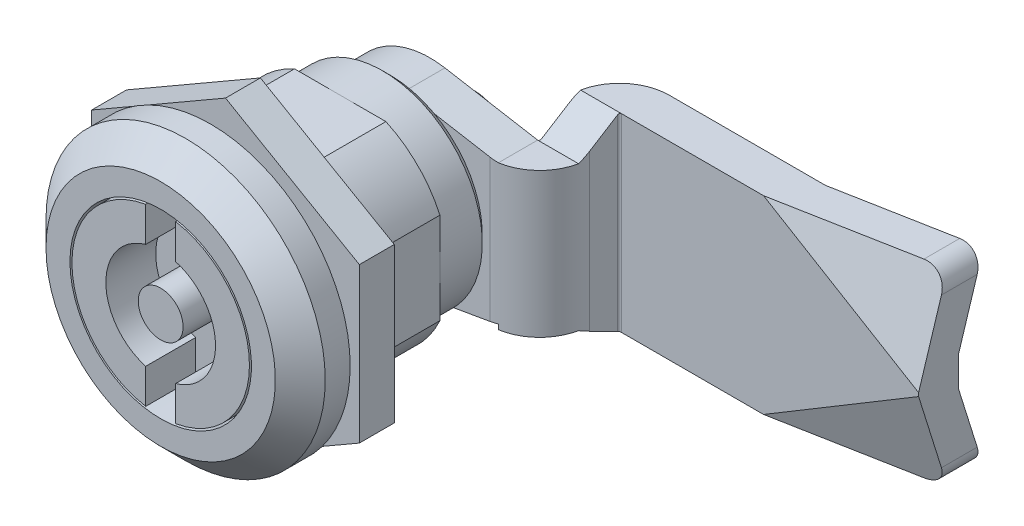
SolidWorks part; units mm, degrees
material "Alloy Steel"
ref_plane "Front Plane" through (0, 0, 0) normal (0, 0, 1) x (1, 0, 0)
ref_plane "Top Plane" through (0, 0, 0) normal (0, 1, 0) x (1, 0, 0)
ref_plane "Right Plane" through (0, 0, 0) normal (1, 0, 0) x (0, 0, -1)
sketch "Sketch1" plane through (0, 0, 0) normal (0, 0, 1) x (1, 0, 0)
  circle A0 centre (0, 0) radius 14
  dimension "D1" = 28
extrude "Extrude1" add sketch "Sketch1" against normal blind 5
sketch "Sketch2" plane through (0, 0, -5) normal (0, 0, -1) x (-1, 0, 0)
  line L0 (0, 0) -> (0, 14) construction
  line L1 (0, 0) -> (14, 0) construction
  line L2 (4.5826, -10) -> (-4.5826, -10)
  line L3 (10, -4.5826) -> (10, 4.5826)
  line L4 (4.5826, 10) -> (-4.5826, 10)
  line L5 (-10, -4.5826) -> (-10, 4.5826)
  arc A0 (-10, -4.5826) -> (-4.5826, -10) centre (0, 0) ccw
  arc A1 (-4.5826, 10) -> (-10, 4.5826) centre (0, 0) ccw
  arc A2 (10, 4.5826) -> (4.5826, 10) centre (0, 0) ccw
  arc A3 (4.5826, -10) -> (10, -4.5826) centre (0, 0) ccw
  circle A4 centre (0, 0) radius 14 construction
  dimension "D1" = 22
  dimension "D3" = 20
  dimension "D2" = 20
extrude "Extrude2" add sketch "Sketch2" along normal blind 18
ref_plane "Plane1" through (0, 0, -25) normal (0, 0, 1) x (1, 0, 0)
ref_plane "Plane2" through (0, 0, -6.5) normal (0, 0, -1) x (-1, 0, 0)
sketch "Sketch7" plane through (0, 0, -6.5) normal (0, 0, -1) x (-1, 0, 0)
  line L1 (0, 15.5) -> (-13.4234, 7.75)
  line L2 (-13.4234, 7.75) -> (-13.4234, -7.75)
  line L3 (-13.4234, -7.75) -> (0, -15.5)
  line L4 (0, -15.5) -> (13.4234, -7.75)
  line L5 (13.4234, -7.75) -> (13.4234, 7.75)
  line L6 (13.4234, 7.75) -> (0, 15.5)
  circle A0 centre (0, 0) radius 13.4234 construction
  circle A1 centre (0, 0) radius 11.1
  dimension "D2" = 22.2
  dimension "D1" = 31
extrude "Extrude6" add sketch "Sketch7" along normal blind 3.5 separate body
sketch "Sketch10" plane through (0, 0, 0) normal (1, 0, 0) x (0, 0, -1)
  line L0 (0, 11.5) -> (0, 14)
  line L1 (0, 14) -> (0, -14) construction
  line L2 (0, 14) -> (2.5, 14)
  line L3 (2.5, 14) -> (0, 11.5)
  line L4 (5, 14) -> (0, 14) construction
  dimension "D1" = 2.5
  dimension "D2" = 2.5
revolve "Cut-Revolve1" cut sketch "Sketch10" angle 360 about axis through (0, 0, -5) along (0, 0, 1)
sketch "Sketch6" plane through (0, 0, 0) normal (0, 0, 1) x (1, 0, 0)
  line L0 (-1.5, 8.8741) -> (-1.5, -8.8741)
  line L1 (1.5, 8.8741) -> (1.5, -8.8741)
  line L2 (0, 0) -> (0, 5.8757) construction
  circle A0 centre (0, 0) radius 2.25
  circle A1 centre (0, 0) radius 5.5
  arc A3 (1.5, 8.8741) -> (-1.5, 8.8741) centre (0, 0) ccw
  arc A4 (-1.5, -8.8741) -> (1.5, -8.8741) centre (0, 0) ccw
  circle A5 centre (0, 0) radius 9 construction
  circle A6 centre (0, 0) radius 11.5 construction
  dimension "D1" = 3
  dimension "D2" = 11
  dimension "D3" = 2.5
  dimension "D4" = 4.5
extrude "Extrude5" cut sketch "Sketch6" against normal blind 5
sketch "Sketch11" plane through (0, 0, 0) normal (0, 1, 0) x (1, 0, 0)
  line L0 (-4.5826, 23) -> (-10, 23) construction
  line L1 (-10, 23) -> (10, 23)
  line L2 (-10, 23) -> (-10, 27)
  line L3 (16, 35) -> (45, 35)
  line L4 (45, 31) -> (45, 35)
  line L5 (0, 0) -> (0, 40.2207) construction
  line L6 (-10, 23) -> (-10, 5) construction
  line L8 (-10, 27) -> (10.8, 27)
  line L9 (11, 30) -> (11, 27.2)
  line L12 (45, 31) -> (15.2, 31)
  line L13 (15, 28) -> (15, 30.8)
  arc A0 (11, 27.2) -> (10.8, 27) centre (10.8, 27.2) cw
  arc A1 (15, 30.8) -> (15.2, 31) centre (15.2, 30.8) cw
  arc A2 (10, 23) -> (15, 28) centre (10, 28) ccw
  arc A3 (16, 35) -> (11, 30) centre (16, 30) ccw
  point P21 (15, 23)
  dimension "D7" = 0.2
  dimension "D8" = 5
  dimension "D1" = 4
  dimension "D2" = 8
  dimension "D3" = 4
  dimension "D4" = 4
  dimension "D5" = 25
  dimension "D6" = 45
extrude "Extrude9" add sketch "Sketch11" along normal mid plane 19 separate body
fillet "Fillet1" radius 8 2 edges at (-10, -9.5, -25) (-10, 9.5, -25)
fillet "Fillet2" radius 3 2 edges at (45, -9.5, -33) (45, 9.5, -33)
sketch "Sketch12" plane through (0, 0, -27) normal (0, 0, -1) x (-1, 0, 0)
  line L5 (-10.8, 9.5) -> (-10.8, -9.5) construction
  line L7 (-10.8, 7) -> (-1.502, 8.6201)
  line L8 (-10.8, -7) -> (-1.502, -8.6201)
  line L9 (-10.8, 7) -> (-10.8, 10.5)
  line L10 (-10.8, 10.5) -> (10.2, 10.5)
  line L11 (10.2, 10.5) -> (10.2, -10.5)
  line L12 (10.2, -10.5) -> (-10.8, -10.5)
  line L13 (-10.8, -10.5) -> (-10.8, -7)
  line L14 (-10.8, 7) -> (-10.8, -7) construction
  arc A0 (-1.502, -8.6201) -> (-1.502, 8.6201) centre (0, 0) ccw
  point P6 (10.2, 0)
  point P14 (-10.8, 0)
  dimension "D1" = 17.5
  dimension "D4" = 21
  dimension "D2" = 14
  dimension "D3" = 21
extrude "Cut-Extrude1" cut sketch "Sketch12" against normal blind 4
sketch "Sketch14" plane through (10.8, 0, 0) normal (-1, 0, 0) x (0, 0, 1)
  line L0 (-31, 9.5) -> (-23, 9.5)
  line L1 (-23, 10) -> (-23, 4.5826) construction
  line L2 (-23, -8.75) -> (-23, 8.75) construction
  line L3 (-23, 9.5) -> (-23, 7)
  line L5 (-31, -9.5) -> (-23, -9.5)
  line L6 (-23, -4.5826) -> (-23, -10) construction
  line L7 (-23, -9.5) -> (-23, -7.5)
  line L9 (-23, 7) -> (-27, 7)
  line L10 (-27, 7) -> (-31, 9.5)
  line L11 (-23, -7.5) -> (-27, -7.5)
  line L12 (-27, 8.75) -> (-27, -8.75) construction
  line L13 (-27, 7) -> (-27, -7) construction
  line L14 (-27, -7.5) -> (-31, -9.5)
  line L15 (-27, -9.5) -> (-23.0644, -9.5) construction
  line L16 (-30, 9.5) -> (-35, 9.5) construction
  point P14 (-25, -7.5)
  dimension "D1" = 2
  dimension "D2" = 8
extrude "Cut-Extrude2" cut sketch "Sketch14" against normal blind 5
sketch "Sketch17" plane through (45, 0, 0) normal (1, 0, 0) x (0, 0, -1)
  line L0 (27, 7) -> (27, 8.6201) construction
  line L1 (31, 9.5) -> (37.5, 9.5)
  line L2 (31, 9.5) -> (31, -9.5)
  line L3 (31, -9.5) -> (37.5, -9.5)
  line L4 (37.5, 9.5) -> (37.5, -9.5)
  dimension "D1" = 19
  dimension "D2" = 10.5
extrude "Boss-Extrude1" add sketch "Sketch17" against normal blind 15
sketch "Sketch18" plane through (0, 0, -37.5) normal (0, 0, -1) x (-1, 0, 0)
  line L0 (-30, 9.5) -> (-30, -9.5)
  line L1 (-30, -9.5) -> (-45, -9.5) construction
  line L2 (-30, -9.5) -> (-30, 9.5) construction
  line L3 (-30, -9.5) -> (-45, -1.5)
  line L4 (-45, -9.5) -> (-45, 9.5) construction
  line L5 (-45, -1.5) -> (-45, 1.5)
  line L6 (-45, 1.5) -> (-30, 9.5)
  point P7 (-45, 0)
  dimension "D1" = 3
extrude "Cut-Extrude4" cut sketch "Sketch18" against normal blind 2.5
ref_plane "Plane4" through (33.75, -20.25, 0) normal (0.8575, -0.5145, 0) x (0, 0, -1)
ref_plane "Plane3" through (33.75, 20.25, 0) normal (0.8575, 0.5145, 0) x (0, 0, -1)
sketch "Sketch20" plane through (33.75, 20.25, 0) normal (0.8575, 0.5145, 0) x (0, 0, -1)
  line L8 (35, -23.5811) -> (37.5, -23.5811)
  line L9 (37.5, -23.5811) -> (37.5, -24.4385)
  line L11 (31, -31.2985) -> (33.9155, -31.2985)
  line L12 (31, -31.2985) -> (37.5, -31.2985) construction
  line L14 (31, -15.0061) -> (31, -31.2985) construction
  line L15 (31, -23.2985) -> (31, -31.2985)
  line L20 (37.5, -31.2985) -> (37.5, -24.4385)
  line L23 (31, -23.2985) -> (33.9155, -31.2985)
  line L24 (35, -23.5811) -> (35, -24.4385)
  line L25 (35, -24.4385) -> (37.5, -31.2985)
  line L26 (35, -21.8661) -> (35, -24.4385) construction
  point P17 (35, -24.0098)
  dimension "D1" = 8
  dimension "D2" = 4
extrude "Cut-Extrude8" cut sketch "Sketch20" against normal through all
sketch "Sketch21" plane through (33.75, -20.25, 0) normal (0.8575, -0.5145, 0) x (0, 0, -1)
  line L0 (31, 31.2985) -> (31, 23.2985)
  line L1 (31, 23.2985) -> (33.9155, 31.2985)
  line L2 (37.5, 31.2985) -> (31, 31.2985) construction
  line L3 (33.9155, 31.2985) -> (31, 31.2985)
  line L4 (37.5, 23.5811) -> (35, 23.5811)
  line L9 (37.5, 31.2985) -> (37.5, 23.5811)
  line L10 (35, 23.5811) -> (35, 24.4385)
  line L11 (35, 24.4385) -> (37.5, 31.2985)
  line L13 (35, 24.4385) -> (35, 21.8661) construction
  dimension "D1" = 8
  dimension "D2" = 4
extrude "Cut-Extrude9" cut sketch "Sketch21" against normal through all
fillet "Fillet3" radius 2 2 edges at (45, -9.5, -35.7077) (45, 9.5, -35.7077)
sketch "Sketch23" plane through (0, 0, 0) normal (0, 1, 0) x (1, 0, 0)
  line L0 (0, 27) -> (0, 30)
  line L1 (1.502, 27) -> (-8.75, 27) construction
  line L2 (0, 30) -> (-3, 30)
  line L3 (0, 27) -> (-5.5, 27)
  line L4 (-5.5, 27) -> (-5.5, 27.5)
  line L5 (-3, 30) -> (-5.5, 27.5)
  dimension "D1" = 5.5
  dimension "D2" = 3
  dimension "D3" = 0.5
  dimension "D4" = 3
revolve "Revolve1" add sketch "Sketch23" angle 360 about L0
sketch "Sketch24" plane through (0, 0, -27) normal (0, 0, -1) x (-1, 0, 0)
  line L0 (10, -4.5826) -> (10, 4.5826) construction
  line L1 (4, 2.3094) -> (0, 4.6188)
  line L2 (0, 4.6188) -> (-4, 2.3094)
  line L3 (-4, 2.3094) -> (-4, -2.3094)
  line L4 (-4, -2.3094) -> (0, -4.6188)
  line L5 (0, -4.6188) -> (4, -2.3094)
  line L6 (4, -2.3094) -> (4, 2.3094)
  circle A0 centre (0, 0) radius 4 construction
  dimension "D1" = 8
extrude "Boss-Extrude3" add sketch "Sketch24" along normal blind 4.5
ref_axis "Axis1" through (0, 0, -5) along (0, 0, 1)
ref_plane "Plane5" through (0, 0, 0) normal (-0.5, 0.866, 0) x (-0.866, -0.5, 0)
sketch "Sketch26" plane through (0, 0, 0) normal (-0.5, 0.866, 0) x (-0.866, -0.5, 0)
  line L0 (4.6188, -31.5) -> (3.6188, -31.5)
  line L1 (4.6188, -31.5) -> (2.3094, -31.5) construction
  line L2 (3.6188, -31.5) -> (4.6188, -30.5)
  line L3 (4.6188, -31.5) -> (4.6188, -28.3812) construction
  line L4 (4.6188, -30.5) -> (4.6188, -31.5)
  dimension "D1" = 1
  dimension "D2" = 1
revolve "Cut-Revolve4" cut sketch "Sketch26" angle 360 about axis through (0, 0, -5) along (0, 0, 1)
sketch "Sketch28" plane through (0, 0, -31.5) normal (0, 0, -1) x (-1, 0, 0)
  circle A0 centre (0, 0) radius 3.4
  dimension "D1" = 6.8
extrude "Cut-Extrude11" cut sketch "Sketch28" against normal blind 0.1
sketch "Sketch29" plane through (0, 0, -31.5) normal (0, 0, -1) x (-1, 0, 0)
  line L1 (-5, -0.4) -> (5, -0.4)
  line L2 (-5, -0.4) -> (-5, 0.4)
  line L3 (-5, 0.4) -> (5, 0.4)
  line L4 (5, -0.4) -> (5, 0.4)
  line L5 (-5, -0.4) -> (5, 0.4) construction
  line L6 (-5, 0.4) -> (5, -0.4) construction
  point P0 (0, 0)
  dimension "D1" = 0.8
  dimension "D2" = 10
extrude "Cut-Extrude12" cut sketch "Sketch29" against normal blind 0.35
sketch "Sketch30" plane through (0, 0, -31.4) normal (0, 0, -1) x (-1, 0, 0)
  line L0 (0.4, 0.4) -> (2.25, 0.4)
  line L1 (-0.4, 2.25) -> (0.4, 2.25)
  line L2 (-0.4, 2.25) -> (-0.4, 0.4)
  line L3 (-0.4, -2.25) -> (0.4, -2.25)
  line L4 (0.4, 2.25) -> (0.4, 0.4)
  line L5 (0.4, -0.4) -> (2.25, -0.4)
  line L7 (-2.25, 0.4) -> (-0.4, 0.4)
  line L8 (-2.25, 0.4) -> (-2.25, -0.4)
  line L9 (-2.25, -0.4) -> (-0.4, -0.4)
  line L10 (2.25, 0.4) -> (2.25, -0.4)
  line L13 (-3.9486, -0.4) -> (3.9486, -0.4) construction
  line L15 (-0.4, -0.4) -> (-0.4, -2.25)
  line L16 (0.4, -0.4) -> (0.4, -2.25)
  point P0 (0, 0)
  point P5 (0.2356, -1.325)
  dimension "D1" = 4.5
  dimension "D2" = 0.8
  dimension "D3" = 0.8
  dimension "D4" = 4.5
extrude "Cut-Extrude13" cut sketch "Sketch30" against normal blind 3
chamfer "Chamfer2" distance 2.68 angle 30 4 edges at (0, -2.25, -28.4) (0, 2.25, -28.4) (-2.25, 0, -28.4) (2.25, 0, -28.4)
fillet "Fillet8" radius 0.6 4 edges at (-0.4, -0.4, -29.9) (0.4, -0.4, -29.9) (-0.4, 0.4, -29.9) (0.4, 0.4, -29.9)
fillet "Fillet9" radius 0.5 4 edges at (-2.25, 0, -31.15) (2.25, 0, -31.15) (0, 2.25, -31.4) (0, -2.25, -31.4)
sketch "Sketch32" plane through (0, 0, 0) normal (0, 1, 0) x (1, 0, 0)
  line L0 (9.1, 0) -> (9.1, 5)
  line L1 (-11.5, 0) -> (11.5, 0) construction
  line L2 (9.1, 5) -> (8.9, 5)
  line L3 (8.9, 5) -> (8.9, 0)
  line L4 (8.9, 0) -> (9.1, 0)
  dimension "D1" = 8.9
  dimension "D2" = 0.2
  dimension "D3" = 5
revolve "Cut-Revolve5" cut sketch "Sketch32" angle 360 about axis through (0, 0, -5) along (0, 0, 1)
ref_plane "Plane7" through (0, 0, 0) normal (0.7071, 0.7071, 0) x (0.7071, -0.7071, 0)
sketch "Sketch37" plane through (0, 0, 0) normal (0.7071, 0.7071, 0) x (0.7071, -0.7071, 0)
  line L20 (-11, 23) -> (-11, 18)
  line L21 (-11, 18) -> (-10, 18)
  line L22 (-10, 22.25) -> (-10, 18)
  line L23 (-10.3114, 23) -> (-3.8307, 23) construction
  line L24 (-9.25, 23) -> (-10, 22.25)
  line L25 (-9.25, 23) -> (-11, 23)
  dimension "D1" = 5
  dimension "D2" = 10
  dimension "D3" = 0.75
  dimension "D4" = 0.75
revolve "Cut-Revolve7" cut sketch "Sketch37" angle 360 about axis through (0, 0, -5) along (0, 0, 1)
